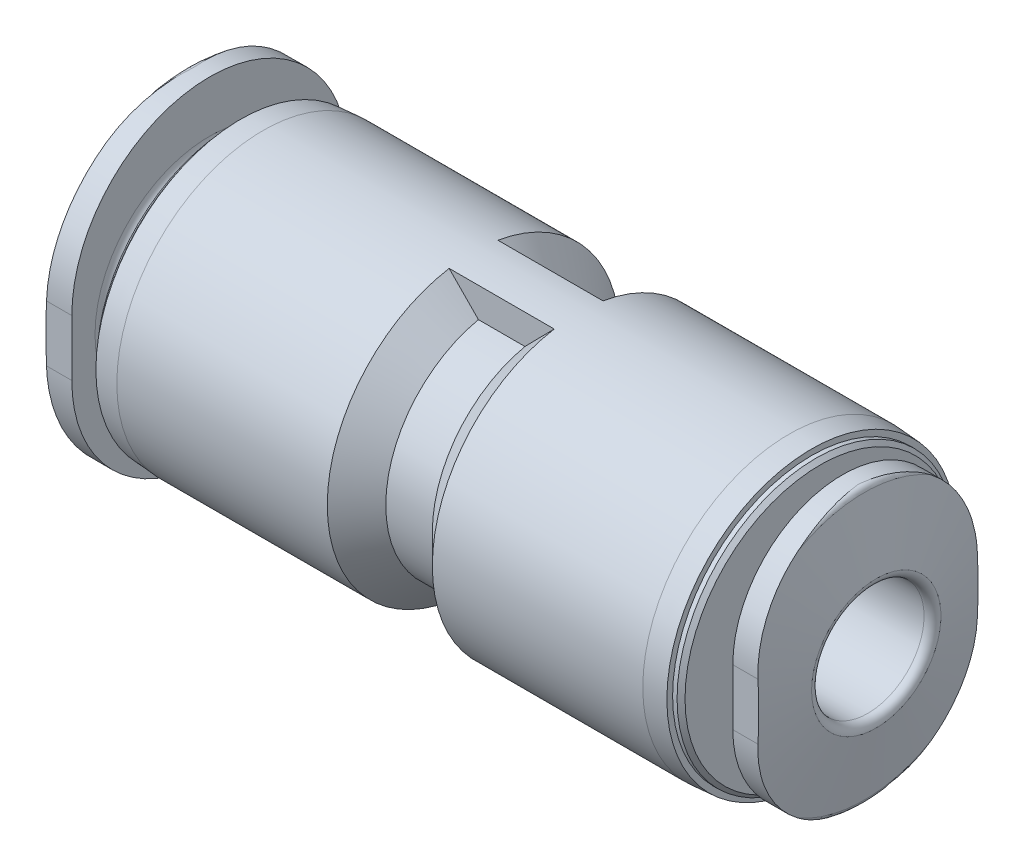
SolidWorks part; units mm, degrees
ref_plane "Ebene vorne" through (0, 0, 0) normal (0, 0, 1) x (1, 0, 0)
ref_plane "Ebene oben" through (0, 0, 0) normal (0, 1, 0) x (1, 0, 0)
ref_plane "Ebene rechts" through (0, 0, 0) normal (1, 0, 0) x (0, 0, -1)
sketch "Skizze1" plane through (0, 0, 0) normal (0, 1, 0) x (1, 0, 0)
  line L0 (-12.45, 0) -> (-12.45, 3.3)
  line L1 (-12.45, 3.3) -> (-12.0207, 5.7347)
  line L2 (-11.8237, 5.9) -> (-11.25, 5.9)
  line L3 (-11.25, 5.9) -> (-11.25, 4.075)
  line L4 (-10.875, 3.7) -> (-10.45, 3.7)
  line L5 (-10.45, 3.7) -> (-10.45, 4.7986)
  line L6 (-10.45, 4.7986) -> (-10.3086, 4.94)
  line L7 (-10.3086, 4.94) -> (-10.15, 4.94)
  line L8 (-10.15, 4.94) -> (-10.15, 5.1441)
  line L9 (-10.15, 5.1441) -> (-9.35, 5.2)
  line L10 (-9.35, 5.2) -> (-1.8675, 5.2)
  line L11 (-1.8675, 5.2) -> (-0.8275, 4.16)
  line L12 (-0.8275, 4.16) -> (0.8275, 4.16)
  line L13 (0.8275, 4.16) -> (1.8675, 5.2)
  line L14 (1.8675, 5.2) -> (9.35, 5.2)
  line L15 (9.35, 5.2) -> (10.15, 5.1441)
  line L16 (10.15, 5.1441) -> (10.15, 4.94)
  line L17 (10.15, 4.94) -> (10.3086, 4.94)
  line L18 (10.3086, 4.94) -> (10.45, 4.7986)
  line L19 (10.45, 4.7986) -> (10.45, 2.5)
  line L20 (10.45, 2.5) -> (10.875, 2.5)
  line L21 (11.25, 2.875) -> (11.25, 4.9)
  line L22 (11.25, 4.9) -> (11.8237, 4.9)
  line L23 (12.0207, 4.7347) -> (12.45, 2.3)
  line L24 (12.45, 2.3) -> (12.45, 0)
  line L25 (12.45, 0) -> (-12.45, 0)
  line L26 (12.45, 0) -> (-12.45, 0) construction
  arc A0 (-12.0207, 5.7347) -> (-11.8237, 5.9) centre (-11.8237, 5.7) cw
  arc A1 (-11.25, 4.075) -> (-10.875, 3.7) centre (-10.875, 4.075) ccw
  arc A2 (10.875, 2.5) -> (11.25, 2.875) centre (10.875, 2.875) ccw
  arc A3 (11.8237, 4.9) -> (12.0207, 4.7347) centre (11.8237, 4.7) cw
revolve "Rotation1" add sketch "Skizze1" angle 360 about L26 reverse direction yes
ref_plane "Ebene1" through (12.45, 0, 0) normal (1, 0, 0) x (0, 0, -1)
ref_plane "Ebene2" through (-12.45, 0, 0) normal (1, 0, 0) x (0, 0, -1)
sketch "Skizze2" plane through (12.45, 0, 0) normal (1, 0, 0) x (0, 0, -1)
  line L0 (-7.08, -7.08) -> (7.08, -7.08)
  line L1 (7.08, -7.08) -> (7.08, 7.08)
  line L2 (7.08, 7.08) -> (-7.08, 7.08)
  line L3 (-7.08, 7.08) -> (-7.08, -7.08)
  line L4 (3.9, -1) -> (3.9, 1)
  line L5 (-3.9, 1) -> (-3.9, -1)
  arc A0 (-3.9, -1) -> (3.9, -1) centre (0, -1) ccw
  arc A1 (3.9, 1) -> (-3.9, 1) centre (0, 1) ccw
sketch "Skizze3" plane through (-12.45, 0, 0) normal (1, 0, 0) x (0, 0, -1)
  line L0 (-7.08, -7.08) -> (7.08, -7.08)
  line L1 (7.08, -7.08) -> (7.08, 7.08)
  line L2 (7.08, 7.08) -> (-7.08, 7.08)
  line L3 (-7.08, 7.08) -> (-7.08, -7.08)
  line L4 (4.9, -1) -> (4.9, 1)
  line L5 (-4.9, 1) -> (-4.9, -1)
  arc A0 (-4.9, -1) -> (4.9, -1) centre (0, -1) ccw
  arc A1 (4.9, 1) -> (-4.9, 1) centre (0, 1) ccw
extrude "Schnitt-Linear austragen1" cut sketch "Skizze2" against normal blind 1.2
extrude "Schnitt-Linear austragen2" cut sketch "Skizze3" along normal blind 1.2
sketch "Skizze4" plane through (0, 0, 0) normal (1, 0, 0) x (0, 0, -1)
  line L0 (-0.8667, -3.8025) -> (-0.8667, -5.1273)
  line L1 (0.8667, -5.1273) -> (0.8667, -3.8025)
  line L2 (0.8667, 3.8025) -> (0.8667, 5.1273)
  line L3 (-0.8667, 5.1273) -> (-0.8667, 3.8025)
  arc A0 (-0.8667, 3.8025) -> (-0.8667, -3.8025) centre (0, 0) ccw
  arc A1 (-0.8667, -5.1273) -> (0.8667, -5.1273) centre (0, 0) ccw
  arc A2 (0.8667, -3.8025) -> (0.8667, 3.8025) centre (0, 0) ccw
  arc A3 (0.8667, 5.1273) -> (-0.8667, 5.1273) centre (0, 0) ccw
  circle A4 centre (0, 0) radius 3.12
extrude "Aufsatz-Linear austragen1" add sketch "Skizze4" against normal blind 1.8675 and the other way blind 1.8675
sketch "Skizze5" plane through (0, 0, 0) normal (0, 0, 1) x (1, 0, 0)
  line L0 (-12.45, 0) -> (-12.45, 3.3)
  line L1 (-12.15, 3) -> (-0.85, 3)
  line L2 (-0.85, 3) -> (-0.85, 1.5)
  line L3 (-0.85, 1.5) -> (0.85, 1.5)
  line L4 (0.85, 1.5) -> (0.85, 2)
  line L5 (0.85, 2) -> (12.15, 2)
  line L6 (12.45, 2.3) -> (12.45, 0)
  line L7 (12.45, 0) -> (-12.45, 0)
  line L8 (12.45, 0) -> (-12.45, 0) construction
  arc A0 (-12.45, 3.3) -> (-12.15, 3) centre (-12.15, 3.3) ccw
  arc A1 (12.15, 2) -> (12.45, 2.3) centre (12.15, 2.3) ccw
revolve "Schnitt-Rotation1" cut sketch "Skizze5" angle 360 about L8 reverse direction yes
ref_plane "QSM XY" through (0, 0, 0) normal (1, 0, 0) x (0, 0, -1)
ref_plane "QSM XZ" through (0, 0, 0) normal (0, -1, 0) x (-1, 0, 0)
ref_plane "QSM YZ" through (0, 0, 0) normal (0, 0, -1) x (-1, 0, 0)
ref_axis "QSM X" through (0, 0, 80.9) along (0, 0, -1)
ref_axis "QSM Y" through (0, -50, 0) along (0, 1, 0)
ref_axis "QSM Z" through (80.9, 0, 0) along (-1, 0, 0)
sketch3d "QSM"
  point P0 (0, 0, 0)
